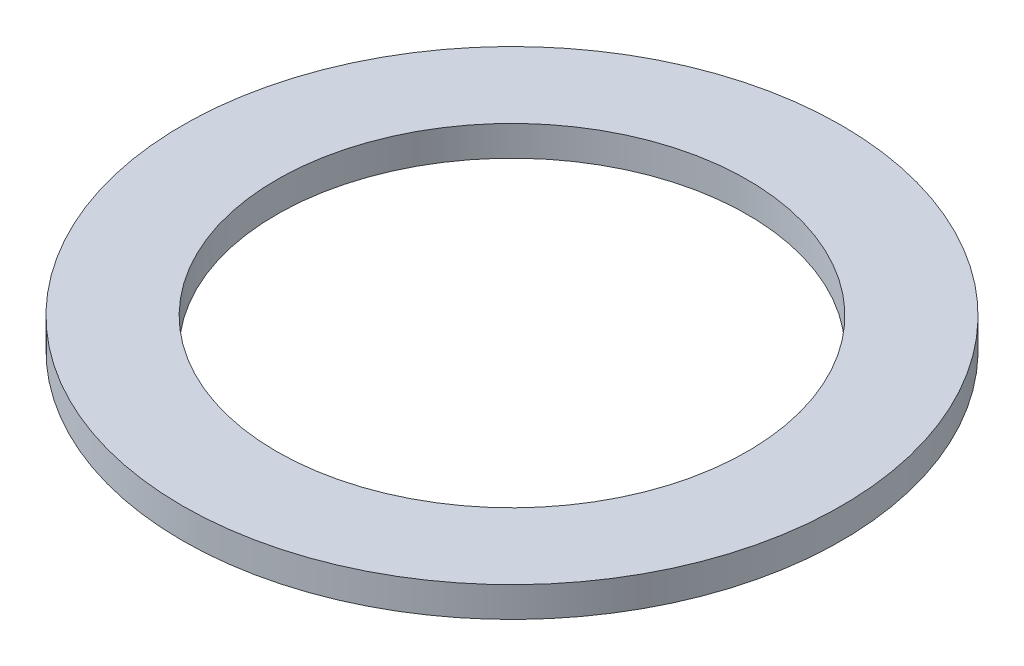
SolidWorks part; units mm, degrees
material "Alum Plate"
ref_plane "Front Plane" through (0, 0, 0) normal (0, 0, 1) x (1, 0, 0)
ref_plane "Top Plane" through (0, 0, 0) normal (0, 1, 0) x (1, 0, 0)
ref_plane "Right Plane" through (0, 0, 0) normal (1, 0, 0) x (0, 0, -1)
other "Bounding Box"
ref_plane "Default Plane" through (-8.9266, -12.7485, 0) normal (-0.1736, 0.9848, 0) x (0.9848, 0.1736, 0)
sketch "Sketch1" plane through (0, 0, 0) normal (0, 1, 0) x (1, 0, 0)
  circle A0 centre (0, 0) radius 7.9375
  circle A1 centre (0, 0) radius 11.1125
  dimension "D1" = 15.875
  dimension "D2" = 22.225
extrude "Boss-Extrude1" add sketch "Sketch1" along normal mid plane 1.016
